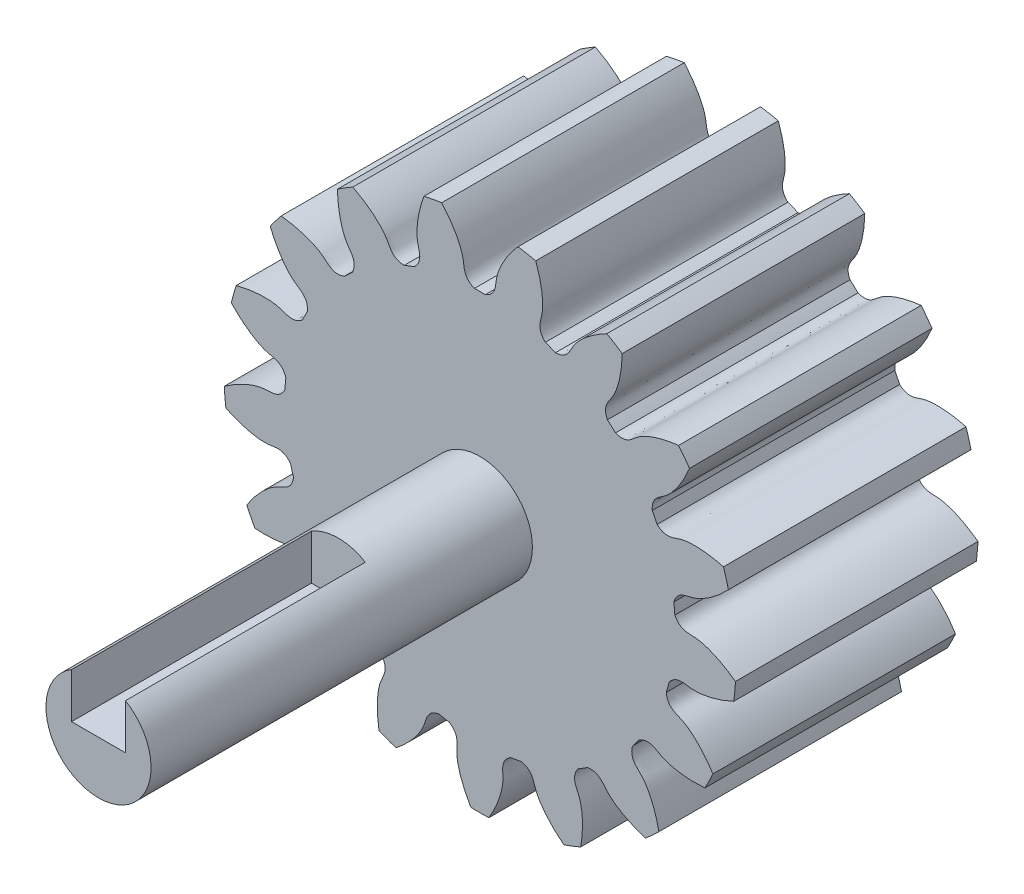
SolidWorks part; units mm, degrees
ref_plane "前视基准面" through (0, 0, 0) normal (0, 0, 1) x (1, 0, 0)
ref_plane "上视基准面" through (0, 0, 0) normal (0, 1, 0) x (1, 0, 0)
ref_plane "右视基准面" through (0, 0, 0) normal (1, 0, 0) x (0, 0, -1)
sketch "草图1" plane through (0, 0, 0) normal (0, 0, 1) x (1, 0, 0)
  circle A0 centre (0, 0) radius 19
extrude "凸台-拉伸1" add sketch "草图1" along normal blind 18
ref_axis "基准轴1" through (0, 0, 18) along (0, 0, -1)
sketch "草图2" plane through (0, 0, 0) normal (0, 0, 1) x (1, 0, 0)
  line L0 (0, 0) -> (0, 19) construction
  circle A0 centre (0, 0) radius 19 construction
  arc A1 (0.4034, 14.4944) -> (-0.4034, 14.4944) centre (0, 0) ccw
  arc A2 (6.2313, 21.4814) -> (-6.2313, 21.4814) centre (0, 0) ccw
  spline S0 degree 3 poles (0.4034, 14.4944) (1.2558, 14.8496) (1.1324, 15.5096) (1.2766, 16.1296) (1.29, 16.1823) (1.306, 16.2408) (1.3251, 16.3052) (1.3474, 16.3752) (1.3731, 16.4508) (1.4025, 16.5319) (1.4359, 16.6184) (1.4733, 16.7101) (1.5152, 16.8068) (1.5616, 16.9086) (1.6128, 17.0151) (1.669, 17.1264) (1.7304, 17.2421) (1.7972, 17.3621) (1.8696, 17.4863) (1.9478, 17.6145) (2.032, 17.7465) (2.1224, 17.8821) (2.2191, 18.0211) (2.3223, 18.1634) (2.4322, 18.3086) (2.5489, 18.4566) (2.6727, 18.6072) (2.8035, 18.7601) (2.9417, 18.9152) (3.0873, 19.0722) (3.2404, 19.2308) (3.4012, 19.3908) (3.5698, 19.552) (3.7462, 19.7141) (3.9307, 19.8769) (4.1233, 20.0401) (4.324, 20.2035) (4.533, 20.3667) (4.7503, 20.5295) (4.9761, 20.6917) (5.2103, 20.853) (5.453, 21.0131) (5.7916, 21.2269) (6.0532, 21.3811) (6.2313, 21.4814) knots 0 0 0 0 0.193883 0.199024 0.204851 0.211363 0.21856 0.226443 0.235011 0.244265 0.254205 0.264829 0.27614 0.288136 0.300817 0.314184 0.328236 0.342973 0.358397 0.374505 0.391299 0.408779 0.426944 0.445795 0.465331 0.485552 0.506459 0.528051 0.550329 0.573293 0.596941 0.621276 0.646296 0.672001 0.698392 0.725468 0.753229 0.781677 0.810809 0.840627 0.871131 0.90232 0.934195 1 1 1 1
  spline S1 degree 3 poles (-0.4034, 14.4944) (-1.2558, 14.8496) (-1.1324, 15.5096) (-1.2766, 16.1296) (-1.29, 16.1823) (-1.306, 16.2408) (-1.3251, 16.3052) (-1.3474, 16.3752) (-1.3731, 16.4508) (-1.4025, 16.5319) (-1.4359, 16.6184) (-1.4733, 16.7101) (-1.5152, 16.8068) (-1.5616, 16.9086) (-1.6128, 17.0151) (-1.669, 17.1264) (-1.7304, 17.2421) (-1.7972, 17.3621) (-1.8696, 17.4863) (-1.9478, 17.6145) (-2.032, 17.7465) (-2.1224, 17.8821) (-2.2191, 18.0211) (-2.3223, 18.1634) (-2.4322, 18.3086) (-2.5489, 18.4566) (-2.6727, 18.6072) (-2.8035, 18.7601) (-2.9417, 18.9152) (-3.0873, 19.0722) (-3.2404, 19.2308) (-3.4012, 19.3908) (-3.5698, 19.552) (-3.7462, 19.7141) (-3.9307, 19.8769) (-4.1233, 20.0401) (-4.324, 20.2035) (-4.533, 20.3667) (-4.7503, 20.5295) (-4.9761, 20.6917) (-5.2103, 20.853) (-5.453, 21.0131) (-5.7916, 21.2269) (-6.0532, 21.3811) (-6.2313, 21.4814) knots 0 0 0 0 0.193883 0.199024 0.204851 0.211363 0.21856 0.226443 0.235011 0.244265 0.254205 0.264829 0.27614 0.288136 0.300817 0.314184 0.328236 0.342973 0.358397 0.374505 0.391299 0.408779 0.426944 0.445795 0.465331 0.485552 0.506459 0.528051 0.550329 0.573293 0.596941 0.621276 0.646296 0.672001 0.698392 0.725468 0.753229 0.781677 0.810809 0.840627 0.871131 0.90232 0.934195 1 1 1 1
extrude "切除-拉伸1" cut sketch "草图2" along normal through all
pattern_circular "阵列(圆周)1" count 17 every 21.176 about axis through (0, 0, 18) along (0, 0, -1) of "切除-拉伸1"
sketch "草图3" plane through (0, 0, 0) normal (0, 0, 1) x (1, 0, 0)
  circle A0 centre (0, 0) radius 17 construction
  dimension "Dn" = 34
sketch "草图4" plane through (0, 0, 18) normal (0, 0, 1) x (1, 0, 0)
  line L1 (-0.9, 4.8) -> (0.9, 4.8)
  line L2 (-0.9, 4.8) -> (-0.9, 0)
  line L3 (-0.9, 0) -> (0.9, 0)
  line L4 (0.9, 4.8) -> (0.9, 0)
  circle A0 centre (0, 0) radius 3.9
  point P7 (0, 0)
  dimension "D1" = 7.8
  dimension "D2" = 4.8
  dimension "D3" = 1.8
extrude "凸台-拉伸3" add sketch "草图4" along normal blind 10.5 contours L2 A0 L4 L3 | L4 A0 L2 L3 region at (0, 1.9327, 18) region at (0, -0.3293, 18)
sketch "草图5" plane through (0, 0, 28.5) normal (0, 0, 1) x (1, 0, 0)
  line L1 (-2, 0) -> (2, 0)
  line L2 (-2, 0) -> (-2, 7.5)
  line L3 (-2, 7.5) -> (2, 7.5)
  line L4 (2, 0) -> (2, 7.5)
  circle A1 centre (0, 0) radius 3.9
  circle A2 centre (0, 0) radius 3.9
  point P4 (0, 0)
  point P5 (0, 0)
  circle M6 centre (0, 0) radius 3.9
  dimension "D1" = 7.5
  dimension "D2" = 4
  dimension "D3" = 0
extrude "凸台-拉伸4" add sketch "草图5" along normal blind 17.8 contours L4 L1 L2 M6 region at (0, -0.8436, 28.5)
